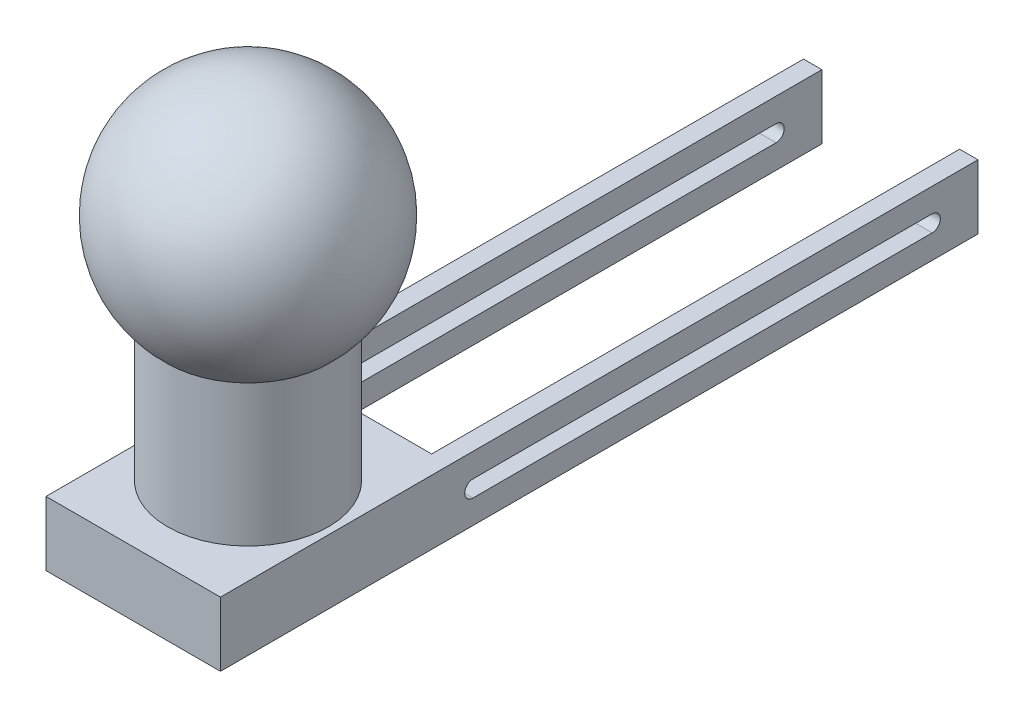
SolidWorks part; units mm, degrees
ref_plane "Front Plane" through (0, 0, 0) normal (0, 0, 1) x (1, 0, 0)
ref_plane "Top Plane" through (0, 0, 0) normal (0, 1, 0) x (1, 0, 0)
ref_plane "Right Plane" through (0, 0, 0) normal (1, 0, 0) x (0, 0, -1)
sketch "Sketch1" plane through (0, 0, 0) normal (0, 1, 0) x (1, 0, 0)
  line L0 (0, 0) -> (0, 88.1944) construction
  line L1 (-19.05, 146.05) -> (-24.13, 146.05)
  line L2 (-24.13, 146.05) -> (-24.13, -63.5)
  line L3 (-24.13, -63.5) -> (24.13, -63.5)
  line L4 (0, -63.5) -> (0, 0) construction
  line L5 (19.05, 0) -> (-19.05, 0)
  line L6 (-19.05, 0) -> (-19.05, 146.05)
  line L7 (24.13, 146.05) -> (24.13, -63.5)
  line L8 (0, -31.75) -> (-24.13, -31.75) construction
  line L9 (19.05, 0) -> (19.05, 146.05)
  line L10 (19.05, 146.05) -> (24.13, 146.05)
  point P15 (-24.13, 163.5379)
  point P16 (0, 0)
  dimension "D1" = 5.08
  dimension "D2" = 19.05
  dimension "D3" = 177.8
  dimension "D4" = 63.5
extrude "Boss-Extrude1" add sketch "Sketch1" against normal blind 17.78
sketch "Sketch3" plane through (0, 0, 0) normal (0, 1, 0) x (1, 0, 0)
  line L0 (0, 0) -> (0, -63.5) construction
  line L1 (19.05, 0) -> (-19.05, 0) construction
  line L2 (-24.13, -63.5) -> (24.13, -63.5) construction
  line L3 (0, -31.75) -> (-24.13, -31.75) construction
  line L4 (-24.13, 146.05) -> (-24.13, -63.5) construction
  circle A0 centre (0, -31.75) radius 22.225
  dimension "D1" = 44.45
extrude "Boss-Extrude2" add sketch "Sketch3" along normal blind 63.5
ref_axis "Axis1" through (0, 63.5, 31.75) along (0, -1, 0)
ref_plane "Plane1" through (0, 0, 31.75) normal (0, 0, 1) x (0, -1, 0)
sketch "Sketch5" plane through (0, 0, 31.75) normal (0, 0, 1) x (0, -1, 0)
  line L0 (-63.5, 0) -> (-63.5, 33.02) construction
  line L1 (-63.5, 22.225) -> (-63.5, -22.225) construction
  line L2 (-63.5, -33.02) -> (-63.5, 33.02)
  arc A0 (-63.5, 33.02) -> (-63.5, -33.02) centre (-63.5, 0) ccw
  dimension "D1" = 33.02
revolve "Revolve1" add sketch "Sketch5" angle 360 about L0
sketch "Sketch6" plane through (-24.13, 0, 0) normal (-1, 0, 0) x (0, 0, 1)
  line L0 (-146.05, -8.89) -> (63.5, -8.89) construction
  line L1 (-146.05, -17.78) -> (-146.05, 0) construction
  line L2 (63.5, -17.78) -> (63.5, 0) construction
  line L3 (-133.35, -8.89) -> (-6.35, -8.89) construction
  line L4 (-133.35, -6.604) -> (-6.35, -6.604)
  line L5 (-133.35, -11.176) -> (-6.35, -11.176)
  arc A0 (-133.35, -6.604) -> (-133.35, -11.176) centre (-133.35, -8.89) ccw
  arc A1 (-6.35, -11.176) -> (-6.35, -6.604) centre (-6.35, -8.89) ccw
  point P8 (-69.85, -8.89)
  dimension "D1" = 4.572
  dimension "D2" = 12.7
  dimension "D3" = 127
extrude "Cut-Extrude1" cut sketch "Sketch6" against normal through all
